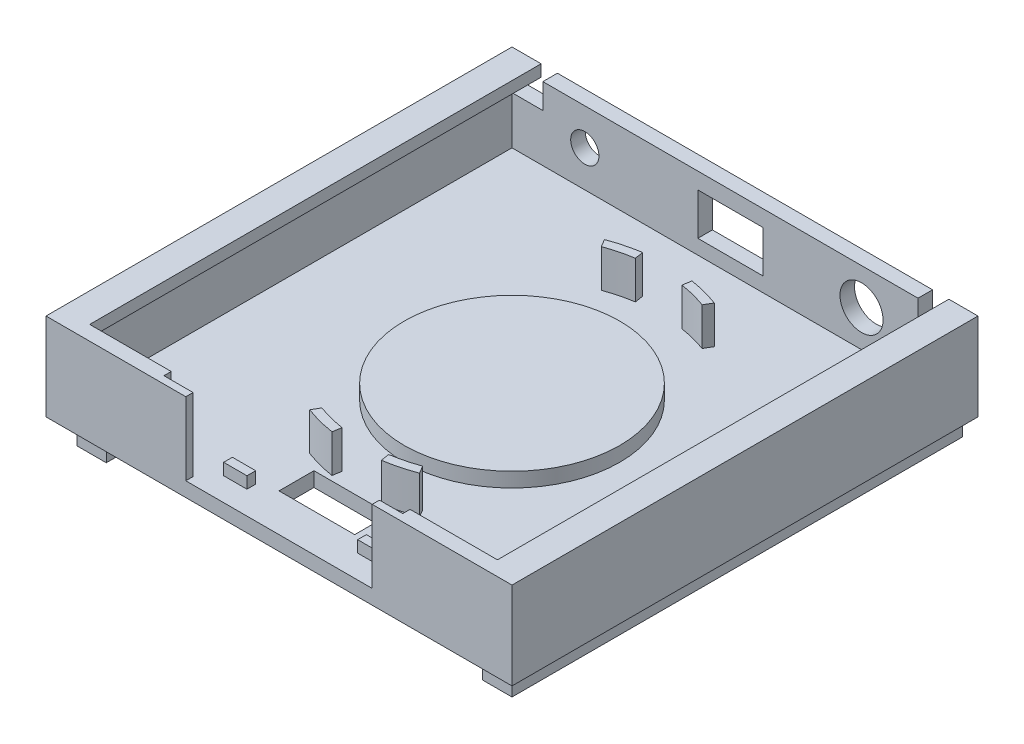
SolidWorks part; units mm, degrees
ref_plane "Front Plane" through (0, 0, 0) normal (0, 0, 1) x (1, 0, 0)
ref_plane "Top Plane" through (0, 0, 0) normal (0, 1, 0) x (1, 0, 0)
ref_plane "Right Plane" through (0, 0, 0) normal (1, 0, 0) x (0, 0, -1)
sketch "Sketch1" plane through (0, 0, 0) normal (0, 1, 0) x (1, 0, 0)
  line L1 (-40, -40) -> (40, -40)
  line L2 (-40, -40) -> (-40, 40)
  line L3 (-40, 40) -> (40, 40)
  line L4 (40, -40) -> (40, 40)
  line L5 (-40, -40) -> (40, 40) construction
  line L6 (-40, 40) -> (40, -40) construction
  point P0 (0, 0)
  dimension "D1" = 80
extrude "Boss-Extrude1" add sketch "Sketch1" along normal blind 2.5
sketch "Sketch2" plane through (0, 2.5, 0) normal (0, 1, 0) x (1, 0, 0)
  line L0 (-3.999, 25.1845) -> (-4.2342, 26.6659)
  line L1 (-8.654, 23.9866) -> (-9.4234, 25.3022)
  line L2 (0, 0) -> (0, -25.5)
  line L3 (0, 0) -> (-25.5, 0)
  line L4 (-3.999, -25.1845) -> (-4.2342, -26.6659)
  line L5 (-8.654, -23.9866) -> (-9.4234, -25.3022)
  line L6 (3.999, -25.1845) -> (4.2342, -26.6659)
  line L7 (8.654, -23.9866) -> (9.4234, -25.3022)
  line L8 (3.999, 25.1845) -> (4.2342, 26.6659)
  line L9 (8.654, 23.9866) -> (9.4234, 25.3022)
  circle A0 centre (0, 0) radius 25.5
  circle A1 centre (0, 0) radius 27
  circle A2 centre (0, 0) radius 18.5
  dimension "D1" = 51
  dimension "D2" = 1.5
  dimension "D3" = 37
sketch "Sketch3" plane through (0, 2.5, 0) normal (0, 1, 0) x (1, 0, 0)
  line L1 (-40, 40) -> (40, 40)
  line L2 (-40, 40) -> (-40, -40)
  line L3 (-40, -40) -> (40, -40)
  line L4 (40, 40) -> (40, -40)
  line L5 (-40, 40) -> (40, -40) construction
  line L6 (-40, -40) -> (40, 40) construction
  line L7 (-37.5, 37.5) -> (37.5, 37.5)
  line L8 (-37.5, 37.5) -> (-37.5, -37.5)
  line L9 (-37.5, -37.5) -> (37.5, -37.5)
  line L10 (37.5, 37.5) -> (37.5, -37.5)
  line L11 (-37.5, 37.5) -> (37.5, -37.5) construction
  line L12 (-37.5, -37.5) -> (37.5, 37.5) construction
  point P0 (0, 0)
  point P7 (0, 0)
  dimension "D1" = 2.5
extrude "Boss-Extrude2" add sketch "Sketch3" along normal blind 12.5
extrude "Boss-Extrude3" add sketch "Sketch2" along normal blind 6.5 contours L0 A1 L1 A0 | L9 A1 L8 A0 | L5 A1 L4 A0 | L6 A1 L7 A0 region at (-6.6031, 2.5, -25.3775) region at (6.6031, 2.5, -25.3775) region at (-6.6031, 2.5, 25.3775) region at (6.6031, 2.5, 25.3775)
sketch "Sketch5" plane through (0, 2.5, 0) normal (0, 1, 0) x (1, 0, 0)
  line L0 (-37.5, -37.5) -> (37.5, -37.5) construction
  line L1 (6.5, -33.5) -> (-6.5, -33.5)
  line L2 (6.5, -33.5) -> (6.5, -27.5)
  line L3 (6.5, -27.5) -> (-6.5, -27.5)
  line L4 (-6.5, -33.5) -> (-6.5, -27.5)
  line L5 (6.5, -33.5) -> (-6.5, -27.5) construction
  line L6 (6.5, -27.5) -> (-6.5, -33.5) construction
  point P0 (0, -30.5)
  dimension "D1" = 4
  dimension "D2" = 13
  dimension "D3" = 6
extrude "Cut-Extrude1" cut sketch "Sketch5" against normal through all contours L3 L4 L1 L2
sketch "Sketch6" plane through (0, 0, 40) normal (0, 0, 1) x (1, 0, 0)
  line L2 (-40, 0) -> (40, 0) construction
  line L3 (-16, 2.5) -> (16, 2.5)
  line L4 (-16, 2.5) -> (-16, 15)
  line L5 (-16, 15) -> (16, 15)
  line L6 (16, 2.5) -> (16, 15)
  line L7 (-16, 2.5) -> (16, 15) construction
  line L8 (-16, 15) -> (16, 2.5) construction
  point P4 (0, 8.75)
  dimension "D1" = 2.5
  dimension "D2" = 32
  dimension "D3" = 12.5
extrude "Cut-Extrude2" cut sketch "Sketch6" against normal up to next contours L6 L5 L4 L3
sketch "Sketch7" plane through (0, 0, -40) normal (0, 0, -1) x (-1, 0, 0)
  line L0 (-40, 0) -> (40, 0) construction
  line L1 (-5.6, 12.2) -> (5.6, 12.2)
  line L2 (-5.6, 12.2) -> (-5.6, 5)
  line L3 (-5.6, 5) -> (5.6, 5)
  line L4 (5.6, 12.2) -> (5.6, 5)
  line L5 (-5.6, 12.2) -> (5.6, 5) construction
  line L6 (-5.6, 5) -> (5.6, 12.2) construction
  point P0 (0, 8.6)
  dimension "D1" = 7.2
  dimension "D2" = 11.2
  dimension "D3" = 5
extrude "Cut-Extrude3" cut sketch "Sketch7" against normal up to next
sketch "Sketch8" plane through (0, 0, 40) normal (0, 0, 1) x (1, 0, 0)
  line L0 (-40, 0) -> (40, 0) construction
  line L1 (-34.8, 0) -> (34.8, 0)
  line L2 (-34.8, 0) -> (-34.8, -2)
  line L3 (-34.8, -2) -> (34.8, -2)
  line L4 (34.8, 0) -> (34.8, -2)
  line L5 (-40, 15) -> (-40, 0) construction
  line L6 (-37.3, -2) -> (37.3, -2)
  line L7 (-37.3, -2) -> (-37.3, -4)
  line L8 (-37.3, -4) -> (37.3, -4)
  line L9 (37.3, -2) -> (37.3, -4)
  line L10 (40, 15) -> (40, 0) construction
  point P14 (-34.8, -1)
  dimension "D1" = 2.5
  dimension "D2" = 2.5
  dimension "D3" = 2.7
  dimension "D4" = 2.7
  dimension "D5" = 2
  dimension "D6" = 2
sketch "Sketch9" plane through (0, 0, -40) normal (0, 0, -1) x (-1, 0, 0)
  line L4 (37.3, -4) -> (-37.3, -4) construction
  line L6 (34.8, 0) -> (-34.8, 0) construction
  line L8 (0, 0) -> (0, -4)
  line L9 (-34.8, 0) -> (-34.8, -2.3)
  line L10 (-34.8, -2.3) -> (-37.35, -2.3)
  line L11 (-37.35, -2.3) -> (-37.35, -4.3)
  line L12 (-37.35, -4.3) -> (-32.3, -4.3)
  line L13 (-32.3, -4.3) -> (-32.3, 0)
  line L14 (-32.3, 0) -> (-34.8, 0)
  line L15 (-40, 15) -> (-40, 0) construction
  line L16 (32.3, -4.3) -> (32.3, 0)
  line L17 (37.35, -4.3) -> (32.3, -4.3)
  line L18 (37.35, -2.3) -> (37.35, -4.3)
  line L19 (34.8, -2.3) -> (37.35, -2.3)
  line L20 (34.8, 0) -> (34.8, -2.3)
  line L21 (32.3, 0) -> (34.8, 0)
  line M17 (-40, 0) -> (40, 0)
  dimension "D1" = 2.3
  dimension "D2" = 2
  dimension "D3" = 2.65
  dimension "D4" = 2.5
extrude "Boss-Extrude4" add sketch "Sketch9" against normal offset from surface (77.35 mm away) 2.65 contours L20 L16 L17 L18 L19 M17 | L12 L13 L9 L10 L11 M17 region at (34.3625, -2.52, -40) region at (-34.3625, -2.52, -40) up to face at (0, 8.125, 40)
sketch "Sketch10" plane through (0, 0, -40) normal (0, 0, -1) x (-1, 0, 0)
  line L0 (-35, 15) -> (-32.2, 15)
  line L1 (-40, 15) -> (40, 15) construction
  line L2 (-32.2, 15) -> (-32.2, 10.7)
  line L3 (-32.2, 10.7) -> (-37.5, 10.7)
  line L4 (-37.5, 10.7) -> (-37.5, 13)
  line L5 (-37.5, 13) -> (-35, 13)
  line L6 (-35, 13) -> (-35, 15)
  line L7 (-40, 15) -> (-40, 0) construction
  line L8 (0, 0) -> (0, 15)
  line L9 (-32.3, 0) -> (32.3, 0) construction
  line L10 (37.5, 13) -> (35, 13)
  line L11 (37.5, 10.7) -> (37.5, 13)
  line L12 (32.2, 10.7) -> (37.5, 10.7)
  line L13 (32.2, 15) -> (32.2, 10.7)
  line L14 (35, 15) -> (32.2, 15)
  line L15 (35, 13) -> (35, 15)
  line M26 (40, 15) -> (-40, 15)
  dimension "D1" = 2.5
  dimension "D2" = 2.3
  dimension "D3" = 2
  dimension "D4" = 2.8
  dimension "D5" = 2.5
extrude "Cut-Extrude4" cut sketch "Sketch10" against normal up to next contours L6 L5 L4 L3 L2 M26 | L10 L15 L13 L12 L11 M26 region at (-34.4565, 12.5268, -40) region at (34.4565, 12.5268, -40)
sketch "Sketch15" plane through (0, 0, -37.5) normal (0, 0, 1) x (1, 0, 0)
  line L1 (37.5, 15) -> (35, 15)
  line L2 (37.5, 15) -> (37.5, 13)
  line L3 (37.5, 13) -> (35, 13)
  line L4 (35, 15) -> (35, 13)
  line L5 (-35, 15) -> (-37.5, 15)
  line L6 (-35, 15) -> (-35, 13)
  line L7 (-35, 13) -> (-37.5, 13)
  line L8 (-37.5, 15) -> (-37.5, 13)
extrude "Boss-Extrude5" add sketch "Sketch15" along normal up to next
extrude "Boss-Extrude6" add sketch "Sketch2<3>" along normal blind 2.5 contours L2 A2 L3 | L3 A2 L2 region at (2.6172, 2.5, -2.6172) region at (-7.8516, 2.5, 7.8516)
sketch "Sketch2<3>" plane through (0, 2.5, 0) normal (0, 1, 0) x (1, 0, 0) same geometry as "Sketch2"
sketch "Sketch16" plane through (0, 0, 37.5) normal (0, 0, -1) x (-1, 0, 0)
  line L0 (37.5, 2.5) -> (16, 2.5) construction
  line L1 (16, 15) -> (21, 15)
  line L2 (16, 15) -> (16, 2.5)
  line L3 (16, 2.5) -> (21, 2.5)
  line L4 (21, 15) -> (21, 2.5)
  line L5 (-16, 2.5) -> (-37.5, 2.5) construction
  line L6 (-16, 15) -> (-20, 15)
  line L7 (-16, 15) -> (-16, 2.5)
  line L8 (-16, 2.5) -> (-20, 2.5)
  line L9 (-20, 15) -> (-20, 2.5)
  dimension "D1" = 5
  dimension "D2" = 4
extrude "Cut-Extrude5" cut sketch "Sketch16" against normal blind 1.25
sketch "Sketch17" plane through (0, 2.5, 0) normal (0, 1, 0) x (1, 0, 0)
  line L0 (-16, -40) -> (16, -40) construction
  line L1 (-13.5, -34.5) -> (-9.5, -34.5)
  line L2 (-13.5, -34.5) -> (-13.5, -36)
  line L3 (-13.5, -36) -> (-9.5, -36)
  line L4 (-9.5, -34.5) -> (-9.5, -36)
  line L5 (9.5, -34.5) -> (13.5, -34.5)
  line L6 (9.5, -34.5) -> (9.5, -36)
  line L7 (9.5, -36) -> (13.5, -36)
  line L8 (13.5, -34.5) -> (13.5, -36)
  line L9 (-6.5, -33.5) -> (-6.5, -27.5) construction
  line L10 (6.5, -33.5) -> (6.5, -27.5) construction
  dimension "D1" = 4
  dimension "D2" = 4
  dimension "D3" = 1.5
  dimension "D4" = 1.5
  dimension "D5" = 4
  dimension "D6" = 3
  dimension "D7" = 3
extrude "Boss-Extrude7" add sketch "Sketch17" along normal blind 2
sketch "Sketch18" plane through (0, 0, -40) normal (0, 0, -1) x (-1, 0, 0)
  line L0 (-37.5, 2.5) -> (37.5, 2.5) construction
  line L3 (-37.5, 10.7) -> (-37.5, 13) construction
  circle A0 centre (-22.5, 8.75) radius 3.4
  circle A1 centre (-22.5, 8.75) radius 3.7
  dimension "D1" = 6.8
  dimension "D2" = 0.3
  dimension "D3" = 6.25
  dimension "D4" = 15
extrude "Cut-Extrude7" cut sketch "Sketch18" against normal up to next contours A1
sketch "Sketch19" plane through (0, 0, -40) normal (0, 0, -1) x (-1, 0, 0)
  line L0 (40, 15) -> (40, 0) construction
  line L1 (-32.2, 15) -> (32.2, 15) construction
  circle A0 centre (25, 8.75) radius 2.425
  dimension "D1" = 4.85
  dimension "D2" = 15
  dimension "D3" = 6.25
extrude "Cut-Extrude8" cut sketch "Sketch19" against normal up to next
